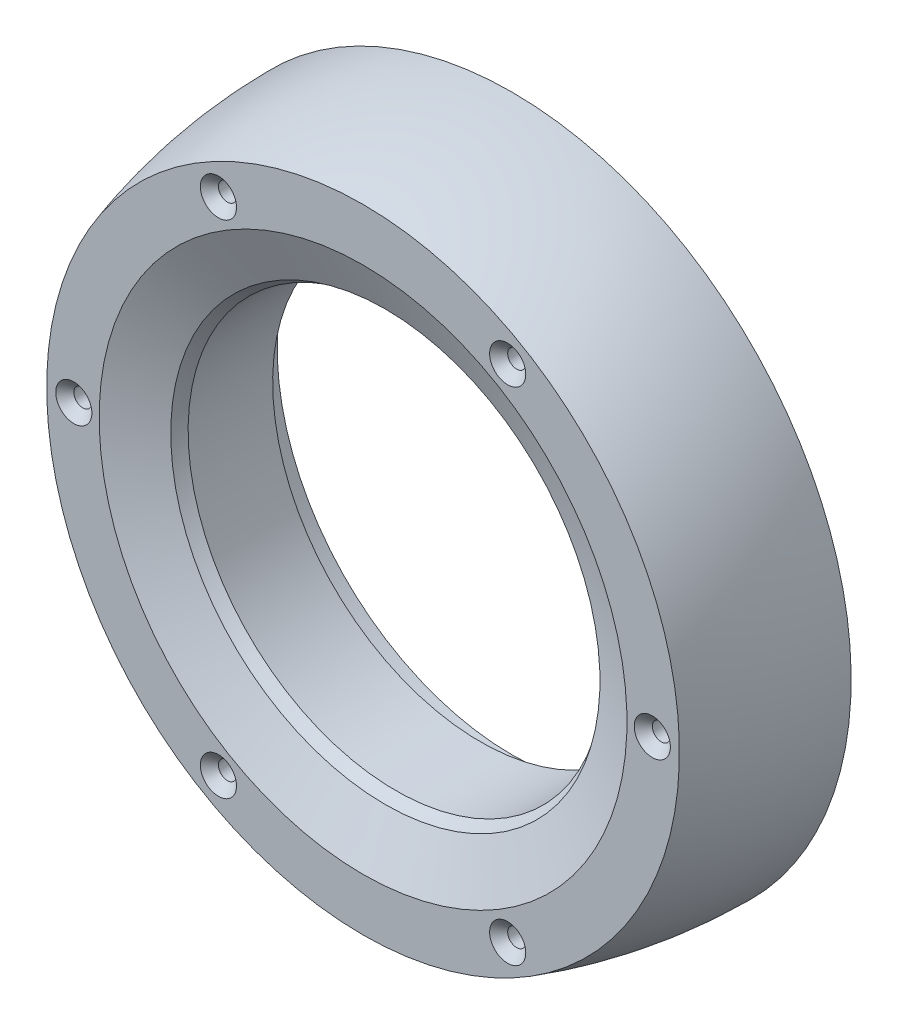
SolidWorks part; units mm, degrees
material "PVC hart"
ref_plane "Ebene vorne" through (0, 0, 0) normal (0, 0, 1) x (1, 0, 0)
ref_plane "Ebene oben" through (0, 0, 0) normal (0, 1, 0) x (1, 0, 0)
ref_plane "Ebene rechts" through (0, 0, 0) normal (1, 0, 0) x (0, 0, -1)
sketch "Skizze1" plane through (0, 0, 0) normal (1, 0, 0) x (0, 0, -1)
  line L0 (0, 26) -> (0, 37.5)
  line L2 (-16.5, 35) -> (-16.5, 24.906)
  line L4 (-3.5, 26) -> (0, 26)
  line L5 (-5.5, 9) -> (-5.5, 23) construction
  line L6 (11.0117, 0) -> (-25.0758, 0) construction
  line L7 (0, 26) -> (0, 0) construction
  line L8 (-3.5, 26) -> (-3.5, 23)
  line L11 (-3.5, 23) -> (-12.8563, 23)
  arc A0 (0, 37.5) -> (-16.5, 35) centre (0, -18.2) ccw
  arc A1 (-16.5, 24.906) -> (-12.8563, 23) centre (-22.5, 9) cw
  arc A2 (-12.8563, 23) -> (-5.5, 9) centre (-22.5, 9) cw construction
  dimension "D7" = 17
  dimension "D8" = 5.5
  dimension "D9" = 55.7
  dimension "D2" = 52
  dimension "D3" = 75
  dimension "D4" = 33
  dimension "D5" = 70
  dimension "D6" = 18
  dimension "D10" = 7
  dimension "D11" = 46
revolve "Rotation" add sketch "Skizze1" angle 360 about L6
chamfer "Fase1" distance 2.5 angle 45 1 edges at (0, 24.906, 16.5) first distance on face at (0, 23, 12.8563)
hole_wizard "M2 Gewinde" [suppressed] positions "Skizze3" profile "Skizze2" tap size "M2" standard "DIN"
sketch "Skizze3" plane through (0, 0, 0) normal (0, 0, -1) x (-1, 0, 0)
  line L23 (-16, 27.7128) -> (-32, 0) construction
  line L24 (-32, 0) -> (-16, -27.7128) construction
  line L25 (-16, -27.7128) -> (16, -27.7128) construction
  line L26 (16, -27.7128) -> (32, 0) construction
  line L27 (32, 0) -> (16, 27.7128) construction
  line L28 (16, 27.7128) -> (-16, 27.7128) construction
  circle A3 centre (0, 0) radius 32 construction
  point P58 (-16, 27.7128)
  point P60 (16, 27.7128)
  point P62 (32, 0)
  point P64 (16, -27.7128)
  point P66 (-16, -27.7128)
  point P68 (-32, 0)
  dimension "D1" = 64
sketch "Skizze2" plane through (16, 27.7128, 0) normal (1, 0, 0) x (0, 1, 0)
  line L0 (0, 0) -> (0, 6.4807)
  line L1 (0, 6.4807) -> (0.8, 6)
  line L2 (0.8, 6) -> (0.8, 0)
  line L5 (0.8, 0) -> (0, 0)
  line L10 (0, 6.4807) -> (-0.8, 6) construction
  line L11 (0, -6.35) -> (0, 107.95) construction
  dimension "Bohrerdurchmesser" = 1.6
  dimension "Bohrungstiefe" = 6
  dimension "Spitzenwinkel" = 118
cosmetic thread "Bohrungsgewinde1" [suppressed] parameters "D1"=4, "D2"=2
cosmetic thread "Bohrungsgewinde2" [suppressed] parameters "D1"=4, "D2"=2
cosmetic thread "Bohrungsgewinde3" [suppressed] parameters "D1"=4, "D2"=2
cosmetic thread "Bohrungsgewinde4" [suppressed] parameters "D1"=4, "D2"=2
cosmetic thread "Bohrungsgewinde5" [suppressed] parameters "D1"=4, "D2"=2
cosmetic thread "Bohrungsgewinde6" [suppressed] parameters "D1"=4, "D2"=2
hole_wizard "M2 Senkung" positions "Skizze5" profile "Skizze4" countersink size "M3" standard "DIN" end condition through all
sketch "Skizze5" plane through (0, 0, 16.5) normal (0, 0, 1) x (1, 0, 0)
  line L1 (-32, 0) -> (-16, -27.7128) construction
  line L2 (-16, -27.7128) -> (16, -27.7128) construction
  line L3 (16, -27.7128) -> (32, 0) construction
  line L4 (32, 0) -> (16, 27.7128) construction
  line L5 (16, 27.7128) -> (-16, 27.7128) construction
  line L6 (-16, 27.7128) -> (-32, 0) construction
  circle A1 centre (0, 0) radius 32 construction
  point P0 (-16, 27.7128)
  point P2 (16, 27.7128)
  point P4 (32, 0)
  point P6 (16, -27.7128)
  point P8 (-16, -27.7128)
  point P10 (-32, 0)
  dimension "D1" = 64
sketch "Skizze4" plane through (-16, 27.7128, 16.5) normal (1, 0, 0) x (0, -1, 0)
  line L0 (0, 0) -> (0, 16.5)
  line L1 (0, 16.5) -> (1, 16.5)
  line L2 (1, 16.5) -> (1, 1)
  line L3 (1, 1) -> (2, 0)
  line L5 (2, 0) -> (0, 0)
  line L6 (-1, 1) -> (-2, 0) construction
  line L11 (0, -6.35) -> (0, 107.95) construction
  dimension "Bohrerdurchmesser" = 2
  dimension "Bohrungstiefe" = 16.5
  dimension "Senkdurchmesser (Oben)" = 4
  dimension "Senkwinkel (Oben)" = 90
